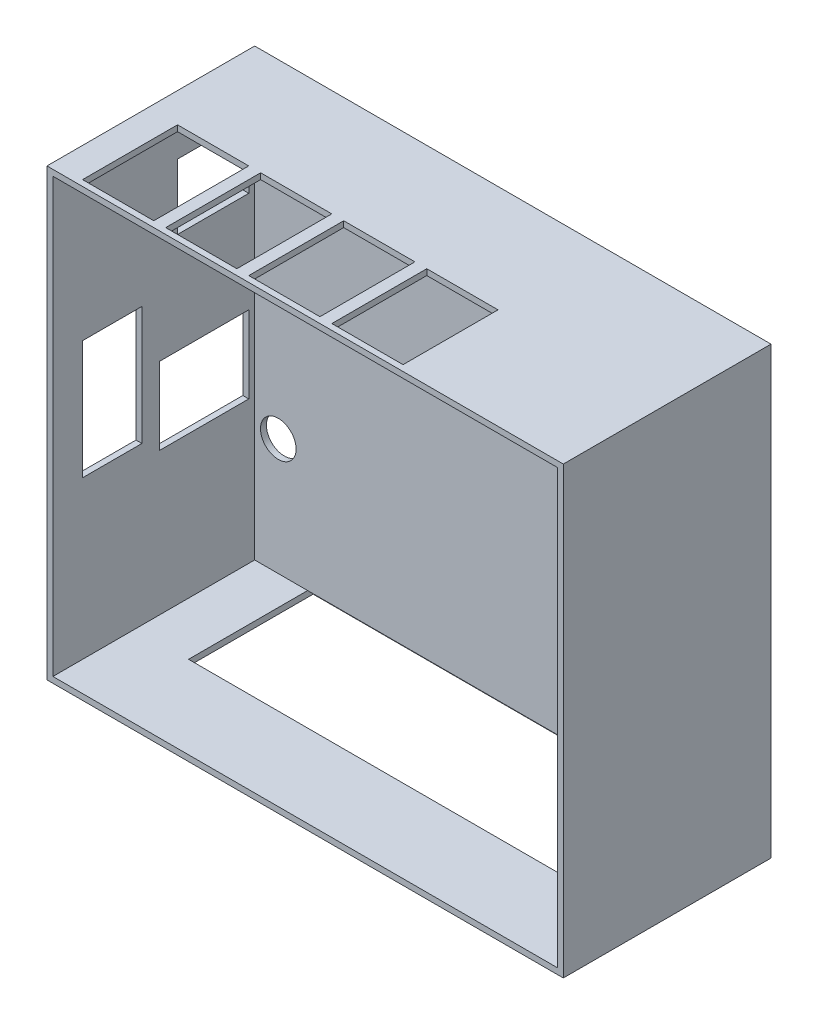
SolidWorks part; units mm, degrees
ref_plane "Plan de face" through (0, 0, 0) normal (0, 0, 1) x (1, 0, 0)
ref_plane "Plan de dessus" through (0, 0, 0) normal (0, 1, 0) x (1, 0, 0)
ref_plane "Plan de droite" through (0, 0, 0) normal (1, 0, 0) x (0, 0, -1)
sketch "Esquisse1" plane through (0, 0, 0) normal (0, 0, 1) x (1, 0, 0)
  line L1 (-132.205, 73) -> (-47.205, 73)
  line L2 (-132.205, 73) -> (-132.205, 0)
  line L3 (-132.205, 0) -> (-47.205, 0)
  line L4 (-47.205, 73) -> (-47.205, 0)
  dimension "D1" = 73
  dimension "D2" = 85
extrude "Boss.-Extru.2" add sketch "Esquisse1" along normal blind 1
sketch "Esquisse6" plane through (-47.205, 0, 0) normal (1, 0, 0) x (0, 0, -1)
  line L1 (0, 73) -> (-35, 73)
  line L2 (0, 73) -> (0, 0)
  line L3 (0, 0) -> (-35, 0)
  line L4 (-35, 73) -> (-35, 0)
  dimension "D1" = 73
  dimension "D2" = 35
extrude "Boss.-Extru.4" add sketch "Esquisse6" along normal blind 1
sketch "Esquisse8" plane through (-132.205, 0, 0) normal (-1, 0, 0) x (0, 0, 1)
  line L1 (0, 73) -> (35, 73)
  line L2 (0, 73) -> (0, 0)
  line L3 (0, 0) -> (35, 0)
  line L4 (35, 73) -> (35, 0)
extrude "Boss.-Extru.6" add sketch "Esquisse8" along normal blind 1
sketch "Esquisse10" plane through (-133.205, 0, 0) normal (-1, 0, 0) x (0, 0, 1)
  line L0 (0, 59.795) -> (2, 59.795) construction
  line L1 (2, 65) -> (14, 65)
  line L2 (2, 65) -> (2, 54)
  line L3 (2, 54) -> (14, 54)
  line L4 (14, 65) -> (14, 54)
  line L5 (0, 73) -> (0, 0) construction
  line L6 (8.5814, 73) -> (8.5814, 65) construction
  line L7 (35, 73) -> (0, 73) construction
  dimension "D1" = 11
  dimension "D2" = 12
extrude "Enlèv. mat.-Extru.1" cut sketch "Esquisse10" against normal blind 1
sketch "Esquisse11" plane through (-133.205, 0, 0) normal (-1, 0, 0) x (0, 0, 1)
  line L0 (11.1338, 0) -> (11.1338, 24) construction
  line L1 (17, 37) -> (2, 37)
  line L2 (17, 37) -> (17, 24)
  line L3 (17, 24) -> (2, 24)
  line L4 (2, 37) -> (2, 24)
  line L5 (0, 0) -> (35, 0) construction
  line L6 (2, 31.8249) -> (0, 31.8249) construction
  line L7 (0, 73) -> (0, 0) construction
  dimension "D1" = 15
  dimension "D2" = 13
extrude "Enlèv. mat.-Extru.2" cut sketch "Esquisse11" against normal blind 1
sketch "Esquisse13" plane through (0, 73, 0) normal (0, 1, 0) x (1, 0, 0)
  line L1 (-133.205, 0) -> (-46.205, 0)
  line L2 (-133.205, 0) -> (-133.205, -35)
  line L3 (-133.205, -35) -> (-46.205, -35)
  line L4 (-46.205, 0) -> (-46.205, -35)
  dimension "D1" = 35
  dimension "D2" = 87
extrude "Boss.-Extru.8" add sketch "Esquisse13" along normal blind 1
sketch "Esquisse14" plane through (0, 74, 0) normal (0, 1, 0) x (1, 0, 0)
  line L0 (-116.2799, -34) -> (-116.2799, -35) construction
  line L1 (-128.207, -18) -> (-116.207, -18)
  line L2 (-128.207, -18) -> (-128.207, -34)
  line L3 (-128.207, -34) -> (-116.207, -34)
  line L4 (-116.207, -18) -> (-116.207, -34)
  line L5 (-133.205, -35) -> (-46.205, -35) construction
  line L6 (-128.207, -21.7805) -> (-133.205, -21.7805) construction
  line L7 (-133.205, 0) -> (-133.205, -35) construction
  line L8 (-122.1939, -35) -> (-122.207, -34)
  line L9 (-123.3121, -18) -> (-123.3121, 0) construction
  line L10 (-46.205, 0) -> (-133.205, 0) construction
  dimension "D1" = 12
  dimension "D2" = 16
extrude "Enlèv. mat.-Extru.3" cut sketch "Esquisse14" against normal blind 1 contours L2 L1 L4 L3
sketch "Esquisse18" plane through (0, 74, 0) normal (0, 1, 0) x (1, 0, 0)
  line L1 (-114.207, -18) -> (-102.207, -18)
  line L2 (-114.207, -18) -> (-114.207, -34)
  line L3 (-114.207, -34) -> (-102.207, -34)
  line L4 (-102.207, -18) -> (-102.207, -34)
  line L6 (-108.207, -18) -> (-108.207, 0) construction
  line L7 (-46.205, 0) -> (-133.205, 0) construction
  line L8 (-116.207, -27.2223) -> (-114.207, -27.2223) construction
  line L9 (-116.207, -18) -> (-116.207, -34) construction
  dimension "D1" = 12
  dimension "D2" = 16
extrude "Enlèv. mat.-Extru.5" cut sketch "Esquisse18" against normal blind 1
sketch "Esquisse20" plane through (0, 74, 0) normal (0, 1, 0) x (1, 0, 0)
  line L0 (-94.6424, 0) -> (-94.6424, -18) construction
  line L1 (-100.207, -18) -> (-88.207, -18)
  line L2 (-100.207, -18) -> (-100.207, -34)
  line L3 (-100.207, -34) -> (-88.207, -34)
  line L4 (-88.207, -18) -> (-88.207, -34)
  line L5 (-46.205, 0) -> (-133.205, 0) construction
  line L6 (-100.207, -27.2382) -> (-102.207, -27.2382) construction
  line L7 (-102.207, -34) -> (-102.207, -18) construction
  dimension "D1" = 12
  dimension "D2" = 16
extrude "Enlèv. mat.-Extru.6" cut sketch "Esquisse20" against normal blind 1
sketch "Esquisse21" plane through (0, 74, 0) normal (0, 1, 0) x (1, 0, 0)
  line L0 (-81.659, 0) -> (-81.659, -18) construction
  line L1 (-86.207, -18) -> (-74.207, -18)
  line L2 (-86.207, -18) -> (-86.207, -34)
  line L3 (-86.207, -34) -> (-74.207, -34)
  line L4 (-74.207, -18) -> (-74.207, -34)
  line L5 (-46.205, 0) -> (-133.205, 0) construction
  line L6 (-86.207, -22.4048) -> (-88.207, -22.4048) construction
  line L7 (-88.207, -34) -> (-88.207, -18) construction
  dimension "D1" = 12
  dimension "D2" = 16
extrude "Enlèv. mat.-Extru.7" cut sketch "Esquisse21" against normal blind 1
sketch "Esquisse22" plane through (0, 0, 1) normal (0, 0, 1) x (1, 0, 0)
  circle A0 centre (-128.3346, 69.1704) radius 3
sketch "Esquisse23" plane through (0, 0, 1) normal (0, 0, 1) x (1, 0, 0)
  circle A0 centre (-128.2288, 19.6605) radius 3
sketch "Esquisse24" plane through (0, 0, 1) normal (0, 0, 1) x (1, 0, 0)
  line L0 (-73.2164, 69.223) -> (-74.2164, 69.223) construction
  circle A0 centre (-70.2164, 69.223) radius 3
sketch "Esquisse25" plane through (0, 0, 0) normal (0, -1, 0) x (1, 0, 0)
  line L1 (-133.205, 35) -> (-46.205, 35)
  line L2 (-133.205, 35) -> (-133.205, 0)
  line L3 (-133.205, 0) -> (-46.205, 0)
  line L4 (-46.205, 35) -> (-46.205, 0)
extrude "Boss.-Extru.11" add sketch "Esquisse25" along normal blind 1
sketch "Esquisse26" plane through (0, -1, 0) normal (0, -1, 0) x (1, 0, 0)
  line L1 (-123.286, 21.0671) -> (-46.286, 21.0671)
  line L2 (-123.286, 21.0671) -> (-123.286, 0.0671)
  line L3 (-123.286, 0.0671) -> (-46.286, 0.0671)
  line L4 (-46.286, 21.0671) -> (-46.286, 0.0671)
  dimension "D1" = 77
  dimension "D2" = 21
extrude "Enlèv. mat.-Extru.13" cut sketch "Esquisse26" against normal blind 1
extrude "Enlèv. mat.-Extru.14" cut sketch "Esquisse23" against normal blind 10
extrude "Enlèv. mat.-Extru.15" cut sketch "Esquisse22" against normal blind 10
extrude "Enlèv. mat.-Extru.18" cut sketch "Esquisse24" against normal blind 10 contours A0
sketch "Esquisse27" plane through (-133.205, 0, 0) normal (-1, 0, 0) x (0, 0, 1)
  line L0 (25, 46.5) -> (25, 74) construction
  line L1 (20, 46.5) -> (30, 46.5)
  line L2 (20, 46.5) -> (20, 26.5)
  line L3 (20, 26.5) -> (30, 26.5)
  line L4 (30, 46.5) -> (30, 26.5)
  line L5 (0, 74) -> (35, 74) construction
  line L6 (25, 26.5) -> (25, -1) construction
  line L7 (35, -1) -> (0, -1) construction
  line L8 (35, 36.5) -> (30, 36.5) construction
  line L9 (35, -1) -> (35, 74) construction
  dimension "D1" = 20
  dimension "D2" = 10
extrude "Enlèv. mat.-Extru.19" cut sketch "Esquisse27" against normal blind 1
